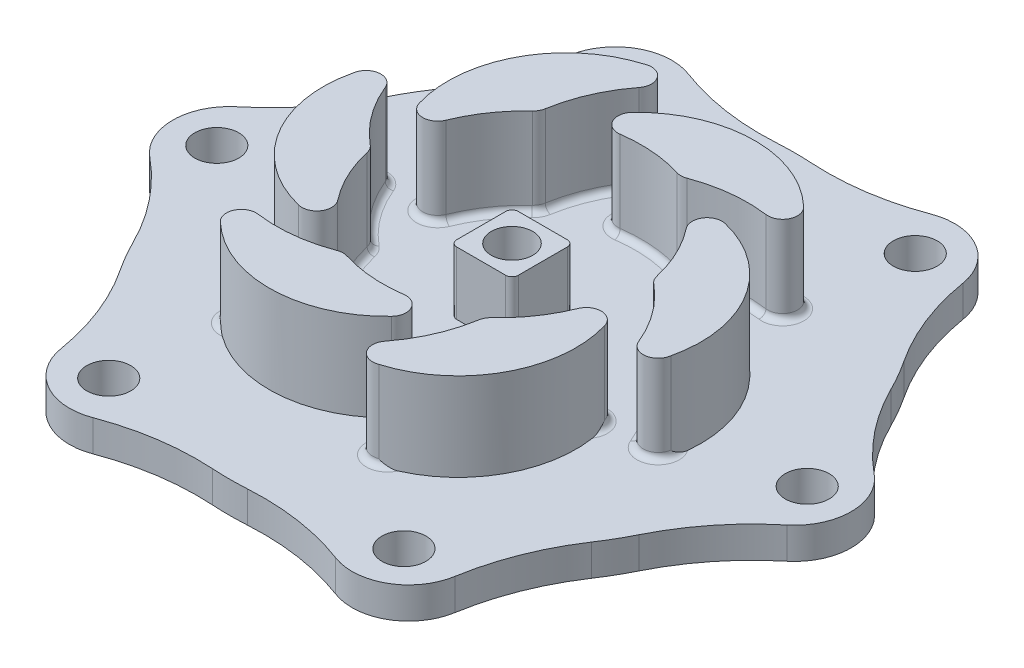
SolidWorks part; units mm, degrees
ref_plane "Front Plane" through (0, 0, 0) normal (0, 0, 1) x (1, 0, 0)
ref_plane "Top Plane" through (0, 0, 0) normal (0, 1, 0) x (1, 0, 0)
ref_plane "Right Plane" through (0, 0, 0) normal (1, 0, 0) x (0, 0, -1)
sketch "Sketch1" plane through (0, 0, 0) normal (0, 1, 0) x (1, 0, 0)
  circle A0 centre (0, 0) radius 25.4
  dimension "D1" = 50.8
extrude "Boss-Extrude1" add sketch "Sketch1" along normal blind 3.175
sketch "Sketch2" plane through (0, 0, 0) normal (0, -1, 0) x (-1, 0, 0)
  circle A0 centre (0, 0) radius 25.4
  circle A1 centre (0, 0) radius 28.575
  circle A2 centre (0, 0) radius 25.4 construction
  dimension "D1" = 3.175
extrude "Boss-Extrude2" add sketch "Sketch2" against normal up to surface (3.175 mm away) up to face at (0, 3.175, 25.4)
sketch "Sketch4" plane through (0, 3.175, 0) normal (0, 1, 0) x (1, 0, 0)
  line L1 (-2.4765, 3.1115) -> (2.4765, 3.1115)
  line L2 (-3.1115, 2.4765) -> (-3.1115, -2.4765)
  line L3 (-2.4765, -3.1115) -> (2.4765, -3.1115)
  line L4 (3.1115, 2.4765) -> (3.1115, -2.4765)
  line L5 (-3.1115, 3.1115) -> (3.1115, -3.1115) construction
  line L6 (-3.1115, -3.1115) -> (3.1115, 3.1115) construction
  line L7 (3.2385, -2.6035) -> (3.2385, 2.6035) construction
  arc A0 (-3.1115, -2.4765) -> (-2.4765, -3.1115) centre (-2.4765, -2.4765) ccw
  arc A1 (2.4765, -3.1115) -> (3.1115, -2.4765) centre (2.4765, -2.4765) ccw
  arc A2 (2.4765, 3.1115) -> (3.1115, 2.4765) centre (2.4765, 2.4765) cw
  arc A3 (-2.4765, 3.1115) -> (-3.1115, 2.4765) centre (-2.4765, 2.4765) ccw
  circle A4 centre (0, 0) radius 2.0955
  point P0 (0, 0)
  dimension "D1" = 0.635
  dimension "D3" = 4.191
  dimension "D2" = 0.127
extrude "Boss-Extrude3" add sketch "Sketch4" along normal blind 6.35
sketch "Sketch5" plane through (0, 3.175, 0) normal (0, 1, 0) x (1, 0, 0)
  circle A0 centre (0, 0) radius 2.0955
  circle A2 centre (0, 0) radius 2.0955 construction
extrude "Cut-Extrude1" cut sketch "Sketch5" against normal through all both and the other way through all
sketch "Sketch6" [suppressed] plane through (0, 3.175, 0) normal (0, 1, 0) x (1, 0, 0)
  arc A0 (-7.5441, 11.644) -> (2.7304, 19.1089) centre (5.7363, 4.1682) cw
  arc A1 (2.7304, 19.1089) -> (3.2314, 16.6188) centre (2.9809, 17.8638) cw
  arc A2 (3.2314, 16.6188) -> (-5.3307, 10.398) centre (5.7363, 4.1682) ccw
  arc A3 (-5.3307, 10.398) -> (-7.5441, 11.644) centre (-6.4374, 11.021) cw
  arc A4 (2.7304, 19.1089) -> (-7.5441, 11.644) centre (5.7363, 4.1682) ccw construction
extrude "Boss-Extrude4" [suppressed] add sketch "Sketch6" along normal up to surface (8.89 mm away)
fillet "Fillet1" [suppressed] radius 0.635
pattern_circular "CirPattern1" [suppressed] count 10 over 360 reverse direction yes of bodies 105
sketch "Sketch7" plane through (0, 3.175, 0) normal (0, 1, 0) x (1, 0, 0)
  arc A0 (-1.546, 12.4834) -> (4.71, 11.9847) centre (0.4656, -1.7703) cw
  arc A1 (4.71, 11.9847) -> (5.6828, 12.0141) centre (5.1535, 13.4219) ccw
  arc A2 (5.6828, 12.0141) -> (12.8507, 12.8218) centre (10.8656, -1.7703) cw
  arc A3 (12.8507, 12.8218) -> (13.9805, 15.4964) centre (13.0535, 14.3121) ccw
  arc A4 (13.9805, 15.4964) -> (-2.8275, 15.0284) centre (5.8118, 6.8148) ccw
  arc A5 (-2.8275, 15.0284) -> (-1.546, 12.4834) centre (-1.7562, 13.9727) ccw
  arc A6 (13.9805, 15.4964) -> (-2.8699, 14.9835) centre (5.8118, 6.8148) ccw construction
  arc A7 (12.8507, 12.8218) -> (13.9805, 15.4964) centre (13.0535, 14.3121) ccw construction
  arc A8 (12.8507, 12.8218) -> (5.6828, 12.0141) centre (10.8656, -1.7703) ccw construction
  arc A15 (4.71, 11.9847) -> (5.6828, 12.0141) centre (5.1535, 13.4219) ccw construction
  arc A16 (4.71, 11.9847) -> (-1.546, 12.4834) centre (0.4656, -1.7703) ccw construction
  arc A17 (-2.8699, 14.9835) -> (-1.546, 12.4834) centre (-1.7562, 13.9727) ccw construction
extrude "Boss-Extrude5" add sketch "Sketch7" along normal up to surface (8.89 mm away)
fillet "Fillet3" radius 0.635 5 edges at (-3.0996, 3.175, -13.2963) (14.439, 3.175, -13.7268) (9.2165, 3.175, -12.8636) (5.1988, 3.175, -11.9185) (1.6095, 3.175, -12.5792)
pattern_circular "CirPattern2" count 6 over 360 about axis through (0, 83.9973, 0) along (0, -1, 0) of "Boss-Extrude5", "Fillet3"
sketch "Sketch8" plane through (0, 3.175, 0) normal (0, 1, 0) x (1, 0, 0)
  line L0 (-28.575, 0) -> (0, 0) construction
  arc A0 (-28.0035, 5.6864) -> (-28.0035, -5.6864) centre (-28.575, 0) ccw
  circle A1 centre (0, 0) radius 28.575 construction
  arc A2 (-28.0035, -5.6864) -> (-28.0035, 5.6864) centre (0, 0) cw
  dimension "D1" = 11.43
extrude "Boss-Extrude6" add sketch "Sketch8" against normal up to surface (3.175 mm away) up to face at (0, 0, 2.0955)
fillet "Fillet4" radius 25.4 2 edges at (-28.0035, 1.5875, 5.6864) (-28.0035, 1.5875, -5.6864)
sketch "Sketch9" plane through (0, 3.175, 0) normal (0, 1, 0) x (1, 0, 0)
  line L0 (-34.29, 0) -> (-25.4, 0) construction
  circle A0 centre (-29.845, 0) radius 2.2225
  arc A1 (-32.2023, 4.4163) -> (-32.2023, -4.4163) centre (-28.575, 0) ccw construction
  circle A2 centre (0, 0) radius 25.4 construction
  dimension "D1" = 4.445
extrude "Cut-Extrude2" cut sketch "Sketch9" against normal through all both and the other way through all
pattern_circular "CirPattern3" count 6 over 360 about axis through (0, 3.175, 0) along (0, -1, 0) of "Boss-Extrude6", "Fillet4", "Cut-Extrude2"
